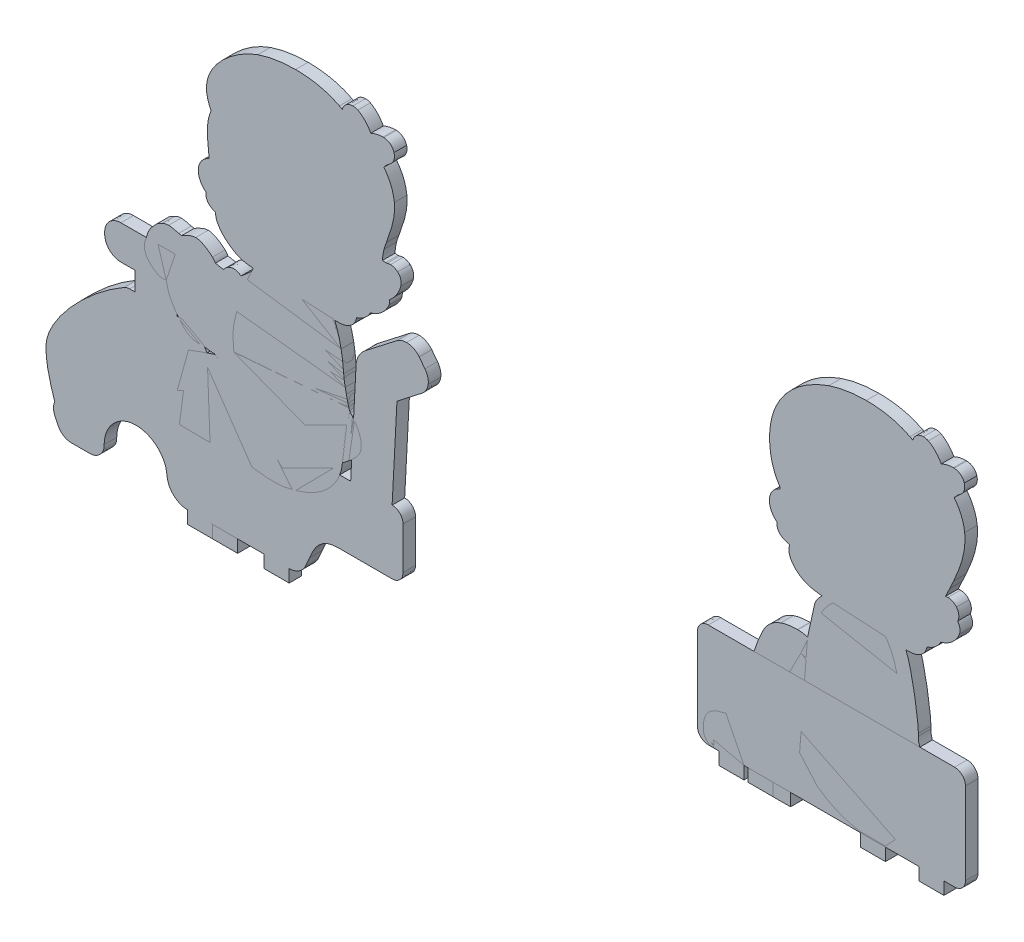
SolidWorks part; units mm, degrees
ref_plane "Front Plane" through (0, 0, 0) normal (0, 0, 1) x (1, 0, 0)
ref_plane "Top Plane" through (0, 0, 0) normal (0, 1, 0) x (1, 0, 0)
ref_plane "Right Plane" through (0, 0, 0) normal (1, 0, 0) x (0, 0, -1)
sketch "D-middle-laser" plane through (0, 0, 0) normal (0, 0, 1) x (1, 0, 0)
  line L0 (289.815, -387.2738) -> (287.7513, -387.2738)
  line L1 (289.9985, -383.7753) -> (289.815, -387.2738)
  line L2 (303.4169, -362.6517) -> (302.3566, -361.2835)
  line L3 (298.2586, -360.7635) -> (292.4293, -365.2856)
  line L4 (290.8054, -368.394) -> (290.3486, -377.102)
  line L5 (288.2912, -329.0773) -> (287.7488, -328.7908)
  line L6 (263.5287, -380.0569) -> (262.5101, -378.5259)
  line L7 (259.6897, -377.0034) -> (258.0098, -377.0034)
  line L8 (258.0098, -377.0034) -> (258.0098, -373.5654)
  line L9 (258.0098, -373.5654) -> (260.3237, -373.5654)
  line L10 (263.2848, -370.6043) -> (263.2848, -370.2876)
  line L11 (260.3237, -367.3265) -> (247.7387, -367.3265)
  line L12 (244.7776, -370.2876) -> (244.7776, -370.6043)
  line L13 (247.7387, -373.5654) -> (250.3211, -373.5654)
  line L14 (250.3211, -373.5654) -> (250.3211, -377.0034)
  line L15 (250.3211, -377.0034) -> (249.3468, -377.0034)
  line L16 (235.6813, -404.0488) -> (236.2843, -405.2726)
  line L17 (238.6679, -406.7577) -> (242.0233, -406.7577)
  line L18 (260.043, -406.7577) -> (278.5385, -406.7577)
  line L19 (287.9321, -398.9652) -> (297.408, -398.9652)
  line L20 (299.404, -396.9619) -> (299.404, -389.2771)
  line L21 (297.408, -387.2738) -> (297.4036, -387.2738)
  line L22 (297.4036, -387.2738) -> (298.292, -370.3419)
  line L23 (298.292, -370.3419) -> (302.8973, -366.7692)
  spline S0 degree 3 poles (287.7513, -387.2738) (288.0017, -386.4926) (288.1406, -385.7436) (288.2176, -385.16) knots 1 1 1 1 2 2 2 2
  spline S1 degree 3 poles (288.2176, -385.16) (288.7789, -384.7782) (289.4211, -384.2968) (289.9985, -383.7753) knots 2 2 2 2 3 3 3 3
  spline S2 degree 3 poles (302.3566, -361.2835) (301.7987, -360.5635) (300.9568, -360.1505) (300.0471, -360.1505) knots 1 1 1 1 2 2 2 2
  spline S3 degree 3 poles (300.0471, -360.1505) (299.4033, -360.1505) (298.7682, -360.3682) (298.2586, -360.7635) knots 2 2 2 2 3 3 3 3
  spline S4 degree 3 poles (292.4293, -365.2856) (291.4615, -366.0364) (290.8697, -367.1693) (290.8054, -368.394) knots 4 4 4 4 5 5 5 5
  spline S5 degree 3 poles (290.3486, -377.102) (290.1562, -376.851) (289.9602, -376.6271) (289.772, -376.4388) knots 6 6 6 6 7 7 7 7
  spline S6 degree 3 poles (289.772, -376.4388) (289.4986, -376.1311) (289.212, -374.765) (289.0223, -373.861) knots 7 7 7 7 8 8 8 8
  spline S7 degree 3 poles (289.0223, -373.861) (288.9555, -373.5426) (288.8874, -373.2183) (288.8144, -372.8929) knots 8 8 8 8 9 9 9 9
  spline S8 degree 3 poles (288.8144, -372.8929) (288.642, -372.1245) (288.5985, -371.5998) (288.5381, -370.8736) knots 9 9 9 9 10 10 10 10
  spline S9 degree 3 poles (288.5381, -370.8736) (288.4675, -370.023) (288.3796, -368.9644) (288.0679, -367.1711) knots 10 10 10 10 11 11 11 11
  spline S10 degree 3 poles (288.0679, -367.1711) (287.8122, -365.7003) (287.3659, -364.3238) (286.8927, -363.1609) knots 11 11 11 11 12 12 12 12
  spline S11 degree 3 poles (286.8927, -363.1609) (287.0416, -363.1791) (287.1753, -363.1899) (287.2919, -363.1959) knots 12 12 12 12 13 13 13 13
  spline S12 degree 3 poles (287.2919, -363.1959) (287.3941, -363.2011) (287.4917, -363.2036) (287.585, -363.2036) knots 13 13 13 13 14 14 14 14
  spline S13 degree 3 poles (287.585, -363.2036) (289.9033, -363.2036) (290.7438, -361.7222) (290.875, -360.8469) knots 14 14 14 14 15 15 15 15
  spline S14 degree 3 poles (290.875, -360.8469) (290.8775, -360.8303) (290.8799, -360.8136) (290.882, -360.797) knots 15 15 15 15 16 16 16 16
  spline S15 degree 3 poles (290.882, -360.797) (292.0577, -360.4417) (292.8744, -359.6931) (293.2711, -359.0262) knots 16 16 16 16 17 17 17 17
  spline S16 degree 3 poles (293.2711, -359.0262) (293.318, -358.9474) (293.3591, -358.8661) (293.3943, -358.783) knots 17 17 17 17 18 18 18 18
  spline S17 degree 3 poles (293.3943, -358.783) (293.4528, -358.7667) (293.511, -358.7498) (293.569, -358.7323) knots 18 18 18 18 19 19 19 19
  spline S18 degree 3 poles (293.569, -358.7323) (296.0101, -357.9939) (296.7701, -356.0179) (296.8488, -355.795) knots 19 19 19 19 20 20 20 20
  spline S19 degree 3 poles (296.8488, -355.795) (296.9513, -355.5043) (296.9891, -355.1985) (296.9622, -354.9012) knots 20 20 20 20 21 21 21 21
  spline S20 degree 3 poles (296.9622, -354.9012) (298.1734, -353.9098) (298.7918, -352.6042) (298.9896, -351.7798) knots 21 21 21 21 22 22 22 22
  spline S21 degree 3 poles (298.9896, -351.7798) (299.1632, -351.0562) (298.9762, -350.2768) (298.4188, -349.786) knots 22 22 22 22 23 23 23 23
  spline S22 degree 3 poles (298.4188, -349.786) (298.0425, -349.4547) (297.588, -349.2746) (297.1195, -349.2746) knots 23 23 23 23 24 24 24 24
  spline S23 degree 3 poles (297.1195, -349.2746) (296.9025, -349.2746) (296.6826, -349.3132) (296.466, -349.3933) knots 24 24 24 24 25 25 25 25
  spline S24 degree 3 poles (296.466, -349.3933) (296.4227, -349.402) (296.3247, -349.4182) (296.1972, -349.4182) knots 25 25 25 25 26 26 26 26
  spline S25 degree 3 poles (296.1972, -349.4182) (296.0085, -349.4182) (295.8332, -349.3836) (295.6743, -349.3152) knots 26 26 26 26 27 27 27 27
  spline S26 degree 3 poles (295.6743, -349.3152) (295.623, -349.011) (295.7022, -348.3839) (295.9104, -347.4465) knots 27 27 27 27 28 28 28 28
  spline S27 degree 3 poles (295.9104, -347.4465) (295.9612, -347.2177) (296.1733, -346.6388) (296.3604, -346.1281) knots 28 28 28 28 29 29 29 29
  spline S28 degree 3 poles (296.3604, -346.1281) (297.0823, -344.158) (298.0708, -341.4599) (297.813, -339.0739) knots 29 29 29 29 30 30 30 30
  spline S29 degree 3 poles (297.813, -339.0739) (297.5826, -336.9415) (296.623, -335.3648) (295.8968, -334.4484) knots 30 30 30 30 31 31 31 31
  spline S30 degree 3 poles (295.8968, -334.4484) (296.1152, -334.128) (296.5186, -333.703) (296.9482, -333.4073) knots 31 31 31 31 32 32 32 32
  spline S31 degree 3 poles (296.9482, -333.4073) (297.6676, -332.9237) (297.99, -332.0327) (297.7527, -331.1969) knots 32 32 32 32 33 33 33 33
  spline S32 degree 3 poles (297.7527, -331.1969) (297.5154, -330.3611) (296.7639, -329.7771) (295.8986, -329.7467) knots 33 33 33 33 34 34 34 34
  spline S33 degree 3 poles (295.8986, -329.7467) (295.8411, -329.7447) (295.7838, -329.7437) (295.7269, -329.7437) knots 34 34 34 34 35 35 35 35
  spline S34 degree 3 poles (295.7269, -329.7437) (294.895, -329.7437) (294.1468, -329.9513) (293.4967, -330.2559) knots 35 35 35 35 36 36 36 36
  spline S35 degree 3 poles (293.4967, -330.2559) (292.8111, -328.9444) (291.8316, -328.1275) (291.1317, -327.7714) knots 36 36 36 36 37 37 37 37
  spline S36 degree 3 poles (291.1317, -327.7714) (290.8428, -327.6244) (290.5346, -327.5546) (290.2308, -327.5546) knots 37 37 37 37 38 38 38 38
  spline S37 degree 3 poles (290.2308, -327.5546) (289.5218, -327.5546) (288.8367, -327.9348) (288.4757, -328.6015) knots 38 38 38 38 39 39 39 39
  spline S38 degree 3 poles (288.4757, -328.6015) (288.3925, -328.7551) (288.3313, -328.915) (288.2912, -329.0773) knots 39 39 39 39 40 40 40 40
  spline S39 degree 3 poles (287.7488, -328.7908) (285.0019, -327.3404) (281.8709, -327.0359) (279.7281, -327.0358) knots 41 41 41 41 42 42 42 42
  spline S40 degree 3 poles (279.7281, -327.0358) (277.2927, -327.0357) (274.84, -327.4258) (272.8218, -328.134) knots 43 43 43 43 44 44 44 44
  spline S41 degree 3 poles (272.8218, -328.134) (270.6039, -328.9125) (268.2296, -330.4012) (266.4707, -332.1165) knots 44 44 44 44 45 45 45 45
  spline S42 degree 3 poles (266.4707, -332.1165) (264.1293, -334.3998) (263.1008, -336.8128) (263.4964, -339.0948) knots 45 45 45 45 46 46 46 46
  spline S43 degree 3 poles (263.4964, -339.0948) (263.6216, -339.8165) (263.8793, -340.5475) (264.2658, -341.2784) knots 46 46 46 46 47 47 47 47
  spline S44 degree 3 poles (264.2658, -341.2784) (264.0578, -341.7935) (263.8519, -342.4295) (263.7162, -343.1598) knots 47 47 47 47 48 48 48 48
  spline S45 degree 3 poles (263.7162, -343.1598) (263.4474, -344.6049) (263.6585, -346.8017) (263.8775, -348.7474) knots 48 48 48 48 49 49 49 49
  spline S46 degree 3 poles (263.8775, -348.7474) (263.8922, -348.8774) (263.9054, -348.9946) (263.9165, -349.096) knots 49 49 49 49 50 50 50 50
  spline S47 degree 3 poles (263.9165, -349.096) (263.3073, -349.3249) (262.7746, -349.7324) (262.4163, -350.2673) knots 50 50 50 50 51 51 51 51
  spline S48 degree 3 poles (262.4163, -350.2673) (261.8528, -351.1083) (261.7663, -352.1733) (262.1788, -353.1892) knots 51 51 51 51 52 52 52 52
  spline S49 degree 3 poles (262.1788, -353.1892) (262.4294, -353.8064) (262.8184, -354.3024) (263.3046, -354.6489) knots 52 52 52 52 53 53 53 53
  spline S50 degree 3 poles (263.3046, -354.6489) (263.2765, -354.8621) (263.2826, -355.0805) (263.3246, -355.2958) knots 53 53 53 53 54 54 54 54
  spline S51 degree 3 poles (263.3246, -355.2958) (263.431, -355.841) (263.7581, -356.3174) (264.228, -356.6112) knots 54 54 54 54 55 55 55 55
  spline S52 degree 3 poles (264.228, -356.6112) (264.3474, -356.6859) (264.6348, -356.8483) (265.0896, -357.0027) knots 55 55 55 55 56 56 56 56
  spline S53 degree 3 poles (265.0896, -357.0027) (265.0759, -357.1621) (265.0811, -357.3246) (265.1067, -357.4867) knots 56 56 56 56 57 57 57 57
  spline S54 degree 3 poles (265.1067, -357.4867) (265.3252, -358.871) (266.6206, -360.3913) (268.5721, -361.5535) knots 57 57 57 57 58 58 58 58
  spline S55 degree 3 poles (268.5721, -361.5535) (269.4092, -362.052) (270.5449, -362.3431) (271.9558, -362.4217) knots 58 58 58 58 59 59 59 59
  spline S56 degree 3 poles (271.9558, -362.4217) (270.3159, -365.6075) (268.7289, -370.9204) (268.3691, -373.4038) knots 59 59 59 59 60 60 60 60
  spline S57 degree 3 poles (268.3691, -373.4038) (268.1946, -374.6086) (268.289, -375.6163) (268.3648, -376.4259) knots 60 60 60 60 61 61 61 61
  spline S58 degree 3 poles (268.3648, -376.4259) (268.4004, -376.8065) (268.4485, -377.3203) (268.4109, -377.507) knots 61 61 61 61 62 62 62 62
  spline S59 degree 3 poles (268.4109, -377.507) (268.41, -377.5078) (268.409, -377.5087) (268.408, -377.5096) knots 62 62 62 62 63 63 63 63
  spline S60 degree 3 poles (268.408, -377.5096) (267.8011, -378.0511) (267.3856, -378.557) (267.1083, -379.019) knots 63 63 63 63 64 64 64 64
  spline S61 degree 3 poles (267.1083, -379.019) (265.5866, -379.3829) (264.3897, -379.7552) (263.5287, -380.0569) knots 64 64 64 64 65 65 65 65
  spline S62 degree 3 poles (262.5101, -378.5259) (261.8831, -377.5723) (260.8296, -377.0034) (259.6897, -377.0034) knots 66 66 66 66 67 67 67 67
  spline S63 degree 3 poles (260.3237, -373.5654) (261.9565, -373.5654) (263.2848, -372.2371) (263.2848, -370.6043) knots 70 70 70 70 71 71 71 71
  spline S64 degree 3 poles (263.2848, -370.2876) (263.2848, -368.6548) (261.9565, -367.3265) (260.3237, -367.3265) knots 72 72 72 72 73 73 73 73
  spline S65 degree 3 poles (247.7387, -367.3265) (246.106, -367.3265) (244.7776, -368.6548) (244.7776, -370.2876) knots 74 74 74 74 75 75 75 75
  spline S66 degree 3 poles (244.7776, -370.6043) (244.7776, -372.2371) (246.106, -373.5654) (247.7387, -373.5654) knots 76 76 76 76 77 77 77 77
  spline S67 degree 3 poles (249.3468, -377.0034) (248.9989, -377.0034) (248.6571, -377.0946) (248.3552, -377.2681) knots 80 80 80 80 81 81 81 81
  spline S68 degree 3 poles (248.3552, -377.2681) (241.2374, -381.3575) (234.5679, -388.7784) (234.0825, -393.1489) knots 81 81 81 81 82 82 82 82
  spline S69 degree 3 poles (234.0825, -393.1489) (233.7752, -395.9162) (234.9563, -399.8057) (235.6424, -401.7681) knots 82 82 82 82 83 83 83 83
  spline S70 degree 3 poles (235.6424, -401.7681) (235.3137, -402.4919) (235.3233, -403.322) (235.6813, -404.0488) knots 83 83 83 83 84 84 84 84
  spline S71 degree 3 poles (236.2843, -405.2726) (236.7357, -406.1886) (237.649, -406.7577) (238.6679, -406.7577) knots 85 85 85 85 86 86 86 86
  spline S72 degree 3 poles (242.0233, -406.7577) (242.8394, -406.7577) (243.5707, -406.3871) (244.0588, -405.8049) knots 87 87 87 87 88 88 88 88
  spline S73 degree 3 poles (244.0588, -405.8049) (244.4475, -405.3411) (244.6819, -404.8566) (244.6819, -404.0353) knots 88 88 88 88 89 89 89 89
  spline S74 degree 3 poles (244.6819, -404.0353) (244.721, -400.7145) (247.3433, -398.042) (250.4935, -398.042) knots 89 89 89 89 90 90 90 90
  spline S75 degree 3 poles (250.4935, -398.042) (252.901, -398.0452) (255.0156, -399.5006) (255.888, -401.7055) knots 90 90 90 90 91 91 91 91
  spline S76 degree 2 poles (255.888, -401.7055) (256.0263, -402.0573) (256.1904, -403.1652) knots 91 91 91 92 92 92
  spline S77 degree 3 poles (256.1904, -403.1652) (256.3332, -405.1702) (258.0066, -406.7577) (260.043, -406.7577) knots 92 92 92 92 93 93 93 93
  spline S78 degree 3 poles (278.5385, -406.7577) (279.7927, -406.7577) (280.9282, -406.0673) (281.502, -404.956) knots 94 94 94 94 95 95 95 95
  spline S79 degree 3 poles (281.502, -404.956) (281.7807, -404.4162) (282.0468, -403.8175) (282.2929, -403.1765) knots 95 95 95 95 96 96 96 96
  spline S80 degree 3 poles (282.2929, -403.1765) (283.76, -399.2895) (285.883, -398.9652) (287.9321, -398.9652) knots 96 96 96 96 97 97 97 97
  spline S81 degree 3 poles (297.408, -398.9652) (298.5103, -398.9652) (299.404, -398.0683) (299.404, -396.9619) knots 98 98 98 98 99 99 99 99
  spline S82 degree 3 poles (299.404, -389.2771) (299.404, -388.1707) (298.5103, -387.2738) (297.408, -387.2738) knots 100 100 100 100 101 101 101 101
  spline S83 degree 3 poles (302.8973, -366.7692) (303.5161, -366.2892) (303.9108, -365.5963) (304.0089, -364.8181) knots 104 104 104 104 105 105 105 105
  spline S84 degree 3 poles (304.0089, -364.8181) (304.107, -364.0402) (303.8967, -363.2708) (303.4169, -362.6517) knots 105 105 105 105 106 106 106 106
sketch "D-side-laser" plane through (0, 0, 0) normal (0, 0, 1) x (1, 0, 0)
  line L0 (258.8724, -363.7956) -> (258.3404, -363.713)
  line L1 (264.3225, -399.9794) -> (264.8876, -400.5621)
  line L2 (264.4342, -406.7579) -> (269.1376, -406.7578)
  line L3 (271.7782, -397.5499) -> (271.1682, -396.181)
  spline S0 degree 3 poles (282.6058, -359.1139) (282.1072, -359.1139) (281.6629, -359.1439) (280.9028, -359.3758) knots 0 0 0 0 1 1 1 1
  spline S1 degree 3 poles (280.9028, -359.3758) (271.5883, -360.7479) (274.754, -360.7348) (269.7234, -364.7792) knots 1 1 1 1 2 2 2 2
  spline S2 degree 3 poles (269.7234, -364.7792) (268.7295, -363.9377) (267.4104, -364.1744) (266.5573, -365.3236) knots 2 2 2 2 3 3 3 3
  spline S3 degree 3 poles (266.5573, -365.3236) (266.0018, -365.2869) (266.2521, -365.3272) (265.0515, -365.0781) knots 3 3 3 3 4 4 4 4
  spline S4 degree 3 poles (265.0515, -365.0781) (264.9233, -364.8265) (264.7473, -364.596) (264.5263, -364.3987) knots 4 4 4 4 5 5 5 5
  spline S5 degree 3 poles (264.5263, -364.3987) (264.1269, -364.0354) (262.689, -362.8164) (261.4362, -362.8161) knots 5 5 5 5 6 6 6 6
  spline S6 degree 3 poles (261.4362, -362.8161) (260.6627, -362.8317) (259.8359, -363.2708) (258.8724, -363.7956) knots 6 6 6 6 7 7 7 7
  spline S7 degree 3 poles (258.3404, -363.713) (257.1022, -363.3562) (256.6327, -363.3562) (256.4755, -363.3562) knots 8 8 8 8 9 9 9 9
  spline S8 degree 3 poles (256.4755, -363.3562) (256.009, -363.3545) (255.5534, -363.5026) (255.182, -363.7631) knots 9 9 9 9 10 10 10 10
  spline S9 degree 3 poles (255.182, -363.7631) (254.6194, -363.9475) (254.1374, -364.3086) (253.7967, -364.789) knots 10 10 10 10 11 11 11 11
  spline S10 degree 3 poles (253.7967, -364.789) (253.1126, -365.3355) (252.562, -366.51) (252.3633, -367.5542) knots 11 11 11 11 12 12 12 12
  spline S11 degree 3 poles (252.3633, -367.5542) (251.2923, -369.6011) (253.0842, -371.3132) (254.1131, -371.9161) knots 12 12 12 12 13 13 13 13
  spline S12 degree 3 poles (254.1131, -371.9161) (254.7944, -372.324) (255.3616, -372.4721) (256.0436, -372.2943) knots 13 13 13 13 14 14 14 14
  spline S13 degree 3 poles (256.0436, -372.2943) (256.3107, -373.71) (256.813, -375.173) (257.7301, -376.2928) knots 14 14 14 14 15 15 15 15
  spline S14 degree 3 poles (257.7301, -376.2928) (258.498, -377.1927) (259.0812, -378.1969) (259.9425, -378.7705) knots 15 15 15 15 16 16 16 16
  spline S15 degree 3 poles (259.9425, -378.7705) (260.7019, -379.2722) (261.5154, -379.3398) (262.211, -379.3398) knots 16 16 16 16 17 17 17 17
  spline S16 degree 3 poles (262.211, -379.3398) (262.818, -379.3398) (263.929, -379.4359) (265.0418, -379.5681) knots 17 17 17 17 18 18 18 18
  spline S17 degree 3 poles (265.0418, -379.5681) (263.4796, -380.0296) (262.8507, -380.307) (262.3605, -380.4828) knots 18 18 18 18 19 19 19 19
  spline S18 degree 3 poles (262.3605, -380.4828) (260.2826, -381.1932) (259.1333, -381.6529) (258.7225, -382.1908) knots 19 19 19 19 20 20 20 20
  spline S19 degree 3 poles (258.7225, -382.1908) (257.2004, -383.7907) (255.6448, -385.6617) (255.7607, -387.6755) knots 20 20 20 20 21 21 21 21
  spline S20 degree 3 poles (255.7607, -387.6755) (255.8678, -389.6128) (256.1339, -391.1358) (257.0844, -392.2716) knots 21 21 21 21 22 22 22 22
  spline S21 degree 3 poles (257.0844, -392.2716) (257.2857, -392.512) (257.7556, -393.0903) (258.4579, -393.962) knots 22 22 22 22 23 23 23 23
  spline S22 degree 3 poles (258.4579, -393.962) (257.9307, -396.0861) (258.8359, -397.102) (260.2656, -397.9986) knots 23 23 23 23 24 24 24 24
  spline S23 degree 3 poles (260.2656, -397.9986) (260.3694, -398.1372) (260.5502, -398.4904) (260.6429, -398.7403) knots 24 24 24 24 25 25 25 25
  spline S24 degree 3 poles (260.6429, -398.7403) (261.2099, -400.2596) (262.8754, -400.1649) (264.3225, -399.9794) knots 25 25 25 25 26 26 26 26
  spline S25 degree 3 poles (264.8876, -400.5621) (264.8761, -400.8642) (264.861, -401.1338) (264.8452, -401.3516) knots 27 27 27 27 28 28 28 28
  spline S26 degree 3 poles (264.8452, -401.3516) (263.4303, -401.9602) (263.1095, -403.2632) (263.0497, -404.357) knots 28 28 28 28 29 29 29 29
  spline S27 degree 3 poles (263.0497, -404.357) (263.0013, -405.2419) (263.2871, -406.1472) (264.1169, -406.6049) knots 29 29 29 29 30 30 30 30
  spline S28 degree 3 poles (264.1169, -406.6049) (264.2035, -406.6617) (264.3105, -406.7126) (264.4342, -406.7579) knots 30 30 30 30 31 31 31 31
  spline S29 degree 3 poles (269.1376, -406.7578) (269.5569, -406.6434) (269.7855, -406.5047) (270.0112, -406.3185) knots 32 32 32 32 33 33 33 33
  spline S30 degree 3 poles (270.0112, -406.3185) (270.6944, -405.7549) (271.0964, -404.6437) (271.6198, -403.843) knots 33 33 33 33 34 34 34 34
  spline S31 degree 3 poles (271.6198, -403.843) (274.3801, -402.3954) (273.859, -399.253) (271.7782, -397.5499) knots 34 34 34 34 35 35 35 35
  spline S32 degree 3 poles (271.1682, -396.181) (271.5506, -395.4655) (271.7903, -394.8059) (271.7325, -394.0699) knots 36 36 36 36 37 37 37 37
  spline S33 degree 3 poles (271.7325, -394.0699) (273.8858, -394.3648) (275.621, -394.521) (277.5174, -394.2955) knots 37 37 37 37 38 38 38 38
  spline S34 degree 3 poles (277.5174, -394.2955) (284.5141, -393.074) (287.9402, -389.2172) (288.3042, -385.1014) knots 38 38 38 38 39 39 39 39
  spline S35 degree 3 poles (288.3042, -385.1014) (289.413, -384.337) (290.8287, -383.1821) (291.4061, -382.1228) knots 39 39 39 39 40 40 40 40
  spline S36 degree 3 poles (291.4061, -382.1228) (292.4462, -380.2141) (290.9558, -377.6235) (289.7721, -376.4389) knots 40 40 40 40 41 41 41 41
  spline S37 degree 3 poles (289.7721, -376.4389) (289.361, -375.8714) (289.0546, -373.8832) (288.8143, -372.8924) knots 41 41 41 41 42 42 42 42
  spline S38 degree 3 poles (288.8143, -372.8924) (288.3854, -370.6784) (288.5882, -369.9812) (288.0677, -367.1711) knots 42 42 42 42 43 43 43 43
  spline S39 degree 3 poles (288.0677, -367.1711) (287.4299, -363.5002) (285.4132, -361.626) (284.9419, -360.9759) knots 43 43 43 43 44 44 44 44
  spline S40 degree 3 poles (284.9419, -360.9759) (284.8193, -360.6285) (284.2769, -359.9129) (283.7319, -359.4421) knots 44 44 44 44 45 45 45 45
  spline S41 degree 2 poles (283.7319, -359.4421) (283.311, -359.0814) (282.6058, -359.1139) knots 45 45 45 46 46 46
sketch "M-arm-laser" plane through (0, 0, 0) normal (0, 0, 1) x (1, 0, 0)
  line L0 (364.0273, -389.7021) -> (364.0193, -389.7589)
  line L1 (364.0193, -389.7589) -> (364.0308, -389.9127)
  line L2 (366.6578, -396.3371) -> (370.5698, -396.3371)
  spline S0 degree 3 poles (390.0078, -368.8827) (389.9756, -368.376) (388.9967, -361.5649) (384.207, -360.674) knots 0 0 0 0 1 1 1 1
  spline S1 degree 3 poles (384.207, -360.674) (383.7435, -360.5878) (378.9808, -359.8258) (375.9436, -365.1067) knots 1 1 1 1 2 2 2 2
  spline S2 degree 3 poles (375.9436, -365.1067) (375.5017, -365.875) (372.7612, -372.433) (372.3066, -373.2283) knots 2 2 2 2 3 3 3 3
  spline S3 degree 3 poles (372.3066, -373.2283) (371.926, -373.8946) (371.5017, -374.7354) (371.0913, -375.5485) knots 3 3 3 3 4 4 4 4
  spline S4 degree 3 poles (371.0913, -375.5485) (370.868, -375.9912) (370.5042, -376.7124) (370.2692, -377.1445) knots 4 4 4 4 5 5 5 5
  spline S5 degree 3 poles (370.2692, -377.1445) (370.2019, -377.2683) (370.114, -377.3758) (370.0062, -377.4666) knots 5 5 5 5 6 6 6 6
  spline S6 degree 3 poles (370.0062, -377.4666) (369.515, -377.8805) (368.7547, -378.5709) (368.0371, -379.3182) knots 6 6 6 6 7 7 7 7
  spline S7 degree 3 poles (368.0371, -379.3182) (365.9088, -381.5347) (365.563, -382.7539) (365.488, -383.4783) knots 7 7 7 7 8 8 8 8
  spline S8 degree 3 poles (365.488, -383.4783) (365.4643, -383.7088) (365.4275, -383.9492) (365.3886, -384.2036) knots 8 8 8 8 9 9 9 9
  spline S9 degree 3 poles (365.3886, -384.2036) (365.2827, -384.8957) (365.1611, -385.6904) (365.2595, -386.5255) knots 9 9 9 9 10 10 10 10
  spline S10 degree 3 poles (365.2595, -386.5255) (365.2919, -386.8) (365.221, -387.0788) (365.0645, -387.3068) knots 10 10 10 10 11 11 11 11
  spline S11 degree 3 poles (365.0645, -387.3068) (364.1713, -388.6083) (364.0664, -389.0249) (364.0356, -389.4264) knots 11 11 11 11 12 12 12 12
  spline S12 degree 3 poles (364.0356, -389.4264) (364.0316, -389.4786) (364.0269, -389.56) (364.0273, -389.7021) knots 12 12 12 12 13 13 13 13
  spline S13 degree 3 poles (364.0308, -389.9127) (364.0529, -390.7024) (364.4878, -392.9862) (365.0612, -394.1583) knots 15 15 15 15 16 16 16 16
  spline S14 degree 3 poles (365.0612, -394.1583) (365.2529, -394.5502) (366.2215, -396.3371) (366.6578, -396.3371) knots 16 16 16 16 17 17 17 17
  spline S15 degree 3 poles (370.5698, -396.3371) (370.9408, -396.3371) (372.1858, -394.7129) (372.48, -392.4929) knots 18 18 18 18 19 19 19 19
  spline S16 degree 3 poles (372.48, -392.4929) (372.5415, -392.5076) (372.6526, -392.5375) (372.7238, -392.5566) knots 19 19 19 19 20 20 20 20
  spline S17 degree 3 poles (372.7238, -392.5566) (373.2659, -392.7024) (374.1727, -392.9462) (375.2608, -392.9462) knots 20 20 20 20 21 21 21 21
  spline S18 degree 3 poles (375.2608, -392.9462) (376.6927, -392.9462) (377.9986, -392.5259) (379.1423, -391.6968) knots 21 21 21 21 22 22 22 22
  spline S19 degree 3 poles (379.1423, -391.6968) (381.1661, -390.2294) (381.6345, -389.2488) (382.0015, -388.2084) knots 22 22 22 22 23 23 23 23
  spline S20 degree 3 poles (382.0015, -388.2084) (382.0612, -388.0391) (382.1043, -387.9168) (382.162, -387.8015) knots 23 23 23 23 24 24 24 24
  spline S21 degree 3 poles (382.162, -387.8015) (382.5504, -387.0249) (385.0879, -383.1352) (386.2978, -381.6625) knots 24 24 24 24 25 25 25 25
  spline S22 degree 3 poles (386.2978, -381.6625) (387.6594, -380.0052) (390.4456, -373.507) (390.0078, -368.8827) knots 25 25 25 25 26 26 26 26
sketch "M-middle-laser" plane through (0, 0, 0) normal (0, 0, 1) x (1, 0, 0)
  line L0 (371.6951, -369.8906) -> (371.6119, -369.8911)
  line L1 (356.4013, -396.3342) -> (367.3662, -396.3371)
  line L2 (370.1145, -391.8785) -> (369.9936, -391.2546)
  line L3 (392.7498, -329.2933) -> (392.2096, -329.0091)
  spline S0 degree 3 poles (384.2217, -327.2663) (381.7955, -327.2663) (379.3515, -327.6537) (377.3398, -328.3572) knots 1 1 1 1 2 2 2 2
  spline S1 degree 3 poles (377.3398, -328.3572) (375.472, -329.0104) (372.7696, -330.2539) (370.5029, -332.4686) knots 2 2 2 2 3 3 3 3
  spline S2 degree 3 poles (370.5029, -332.4686) (367.6335, -335.2722) (366.268, -338.9309) (366.5539, -343.0493) knots 3 3 3 3 4 4 4 4
  spline S3 degree 3 poles (366.5539, -343.0493) (366.6222, -344.0294) (366.7977, -346.5467) (368.4399, -348.9053) knots 4 4 4 4 5 5 5 5
  spline S4 degree 3 poles (368.4399, -348.9053) (368.4506, -349.0003) (368.4603, -349.0864) (368.4687, -349.1629) knots 5 5 5 5 6 6 6 6
  spline S5 degree 3 poles (368.4687, -349.1629) (367.9888, -349.3427) (367.554, -349.6331) (367.2182, -350.0104) knots 6 6 6 6 7 7 7 7
  spline S6 degree 3 poles (367.2182, -350.0104) (366.4491, -350.8755) (366.2696, -352.0769) (366.7375, -353.2251) knots 7 7 7 7 8 8 8 8
  spline S7 degree 3 poles (366.7375, -353.2251) (366.9875, -353.8387) (367.3751, -354.3319) (367.8593, -354.6765) knots 8 8 8 8 9 9 9 9
  spline S8 degree 3 poles (367.8593, -354.6765) (367.8316, -354.8876) (367.8375, -355.1035) (367.8789, -355.3156) knots 9 9 9 9 10 10 10 10
  spline S9 degree 3 poles (367.8789, -355.3156) (367.9846, -355.8556) (368.3129, -356.3316) (368.7796, -356.6221) knots 10 10 10 10 11 11 11 11
  spline S10 degree 3 poles (368.7796, -356.6221) (368.9425, -356.7237) (369.4238, -356.9912) (370.2222, -357.1753) knots 11 11 11 11 12 12 12 12
  spline S11 degree 3 poles (370.2222, -357.1753) (370.0574, -357.5273) (369.9931, -357.9289) (370.0565, -358.3301) knots 12 12 12 12 13 13 13 13
  spline S12 degree 3 poles (370.0565, -358.3301) (370.3279, -360.0446) (372.1776, -361.457) (373.7802, -361.9157) knots 13 13 13 13 14 14 14 14
  spline S13 degree 3 poles (373.7802, -361.9157) (374.5048, -362.1226) (375.3399, -362.2369) (376.1346, -362.2972) knots 14 14 14 14 15 15 15 15
  spline S14 degree 3 poles (376.1346, -362.2972) (375.488, -362.8725) (374.932, -363.5735) (374.7399, -364.3739) knots 15 15 15 15 16 16 16 16
  spline S15 degree 3 poles (374.7399, -364.3739) (374.3171, -366.1349) (373.8433, -368.3076) (373.4728, -370.1577) knots 16 16 16 16 17 17 17 17
  spline S16 degree 3 poles (373.4728, -370.1577) (372.9088, -369.9818) (372.311, -369.8906) (371.6951, -369.8906) knots 17 17 17 17 18 18 18 18
  spline S17 degree 3 poles (371.6119, -369.8911) (370.1433, -369.915) (369.4071, -370.0769) (368.5604, -370.3674) knots 19 19 19 19 20 20 20 20
  spline S18 degree 3 poles (368.5604, -370.3674) (367.0946, -370.8712) (366.0171, -371.8232) (365.2653, -373.2779) knots 20 20 20 20 21 21 21 21
  spline S19 degree 3 poles (365.2653, -373.2779) (364.479, -374.799) (363.5793, -377.3167) (362.8588, -380.0126) knots 21 21 21 21 22 22 22 22
  spline S20 degree 3 poles (362.8588, -380.0126) (361.951, -383.4077) (361.4587, -386.245) (361.3689, -386.7845) knots 22 22 22 22 23 23 23 23
  spline S21 degree 3 poles (361.3689, -386.7845) (361.3088, -387.0825) (361.2325, -387.6097) (361.2823, -388.2025) knots 23 23 23 23 24 24 24 24
  spline S22 degree 3 poles (361.2823, -388.2025) (360.0815, -388.9858) (358.6825, -389.7356) (357.6352, -389.9558) knots 24 24 24 24 25 25 25 25
  spline S23 degree 3 poles (357.6352, -389.9558) (354.7372, -390.5645) (354.2701, -392.7387) (354.3886, -394.4555) knots 25 25 25 25 26 26 26 26
  spline S24 degree 3 poles (354.3886, -394.4555) (354.4617, -395.5092) (355.3458, -396.3342) (356.4013, -396.3342) knots 26 26 26 26 27 27 27 27
  spline S25 degree 3 poles (367.3662, -396.3371) (367.6818, -396.3371) (367.9969, -396.2619) (368.278, -396.1195) knots 28 28 28 28 29 29 29 29
  spline S26 degree 3 poles (368.278, -396.1195) (369.176, -395.6666) (370.5765, -394.262) (370.1145, -391.8785) knots 29 29 29 29 30 30 30 30
  spline S27 degree 3 poles (369.9936, -391.2546) (370.2478, -391.0022) (370.526, -390.708) (370.8469, -390.3611) knots 31 31 31 31 32 32 32 32
  spline S28 degree 3 poles (370.8469, -390.3611) (371.084, -390.1049) (371.3232, -389.8464) (371.4755, -389.7018) knots 32 32 32 32 33 33 33 33
  spline S29 degree 3 poles (371.4755, -389.7018) (371.6049, -389.5788) (371.7614, -389.4349) (371.9315, -389.2785) knots 33 33 33 33 34 34 34 34
  spline S30 degree 3 poles (371.9315, -389.2785) (371.9578, -389.2543) (371.9838, -389.2303) (372.0096, -389.2065) knots 34 34 34 34 35 35 35 35
  spline S31 degree 3 poles (372.0096, -389.2065) (372.5753, -390.2565) (373.1118, -391.0291) (373.613, -391.5138) knots 35 35 35 35 36 36 36 36
  spline S32 degree 3 poles (373.613, -391.5138) (376.8554, -394.6481) (380.9413, -396.3048) (385.4292, -396.3048) knots 36 36 36 36 37 37 37 37
  spline S33 degree 3 poles (385.4292, -396.3048) (390.986, -396.3048) (394.7078, -394.0763) (395.9091, -390.0298) knots 37 37 37 37 38 38 38 38
  spline S34 degree 3 poles (395.9091, -390.0298) (396.7336, -387.251) (397.2485, -384.5859) (395.1899, -380.0981) knots 38 38 38 38 39 39 39 39
  spline S35 degree 3 poles (395.1899, -380.0981) (393.7414, -376.9407) (393.7467, -376.6136) (393.7609, -375.7392) knots 39 39 39 39 40 40 40 40
  spline S36 degree 3 poles (393.7609, -375.7392) (393.7633, -375.5959) (393.7657, -375.4418) (393.7657, -375.2722) knots 40 40 40 40 41 41 41 41
  spline S37 degree 3 poles (393.7657, -375.2722) (393.7657, -373.5678) (392.7231, -366.1031) (391.4727, -363.1352) knots 41 41 41 41 42 42 42 42
  spline S38 degree 3 poles (391.4727, -363.1352) (391.576, -363.1459) (391.6703, -363.1528) (391.7544, -363.1571) knots 42 42 42 42 43 43 43 43
  spline S39 degree 3 poles (391.7544, -363.1571) (391.8557, -363.1622) (391.9521, -363.1645) (392.0443, -363.1645) knots 43 43 43 43 44 44 44 44
  spline S40 degree 3 poles (392.0443, -363.1645) (394.3453, -363.1645) (395.1876, -361.6998) (395.3226, -360.8344) knots 44 44 44 44 45 45 45 45
  spline S41 degree 3 poles (395.3226, -360.8344) (395.3253, -360.8164) (395.3277, -360.7984) (395.3299, -360.7804) knots 45 45 45 45 46 46 46 46
  spline S42 degree 3 poles (395.3299, -360.7804) (396.5036, -360.4277) (397.3181, -359.6801) (397.713, -359.0144) knots 46 46 46 46 47 47 47 47
  spline S43 degree 3 poles (397.713, -359.0144) (397.7589, -358.9376) (397.7991, -358.8583) (397.8336, -358.777) knots 47 47 47 47 48 48 48 48
  spline S44 degree 3 poles (397.8336, -358.777) (397.8923, -358.7608) (397.9505, -358.744) (398.0083, -358.7266) knots 48 48 48 48 49 49 49 49
  spline S45 degree 3 poles (398.0083, -358.7266) (400.4424, -357.993) (401.1972, -356.0307) (401.2752, -355.8094) knots 49 49 49 49 50 50 50 50
  spline S46 degree 3 poles (401.2752, -355.8094) (401.5056, -355.1608) (401.3797, -354.4348) (400.9468, -353.8986) knots 50 50 50 50 51 51 51 51
  spline S47 degree 3 poles (400.9468, -353.8986) (401.2904, -353.2217) (401.2156, -352.3871) (400.7435, -351.7788) knots 51 51 51 51 52 52 52 52
  spline S48 degree 3 poles (400.7435, -351.7788) (400.3702, -351.2977) (399.7826, -351.0104) (399.1718, -351.0103) knots 52 52 52 52 53 53 53 53
  spline S49 degree 3 poles (399.1718, -351.0103) (399.028, -351.0103) (398.885, -351.0257) (398.7451, -351.0564) knots 53 53 53 53 54 54 54 54
  spline S50 degree 3 poles (398.7451, -351.0564) (398.9474, -350.5507) (399.266, -349.8992) (399.4874, -349.4464) knots 54 54 54 54 55 55 55 55
  spline S51 degree 3 poles (399.4874, -349.4464) (399.7389, -348.932) (399.9915, -348.4151) (400.2216, -347.8879) knots 55 55 55 55 56 56 56 56
  spline S52 degree 3 poles (400.2216, -347.8879) (401.2202, -345.6009) (402.5881, -342.4681) (402.2353, -339.2152) knots 56 56 56 56 57 57 57 57
  spline S53 degree 3 poles (402.2353, -339.2152) (402.0061, -337.1026) (401.0428, -335.5308) (400.3259, -334.6262) knots 57 57 57 57 58 58 58 58
  spline S54 degree 3 poles (400.3259, -334.6262) (400.5429, -334.3079) (400.9453, -333.8868) (401.3763, -333.5893) knots 58 58 58 58 59 59 59 59
  spline S55 degree 3 poles (401.3763, -333.5893) (402.0907, -333.0979) (402.4058, -332.2225) (402.17, -331.3982) knots 60 60 60 60 61 61 61 61
  spline S56 degree 3 poles (402.17, -331.3982) (401.9325, -330.567) (401.1922, -329.9879) (400.328, -329.9577) knots 61 61 61 61 62 62 62 62
  spline S57 degree 3 poles (400.328, -329.9577) (400.2702, -329.9559) (400.218, -329.9551) (400.1663, -329.9551) knots 62 62 62 62 63 63 63 63
  spline S58 degree 3 poles (400.1663, -329.9551) (399.4199, -329.955) (398.6686, -330.1298) (397.9462, -330.4635) knots 63 63 63 63 64 64 64 64
  spline S59 degree 3 poles (397.9462, -330.4635) (397.0752, -328.8043) (395.7775, -328.0977) (395.5803, -327.9976) knots 64 64 64 64 65 65 65 65
  spline S60 degree 3 poles (395.5803, -327.9976) (395.3008, -327.8564) (394.9909, -327.7826) (394.6812, -327.7826) knots 65 65 65 65 66 66 66 66
  spline S61 degree 3 poles (394.6812, -327.7826) (393.9536, -327.7825) (393.2846, -328.1791) (392.9355, -328.8177) knots 66 66 66 66 67 67 67 67
  spline S62 degree 3 poles (392.9355, -328.8177) (392.8519, -328.9718) (392.7903, -329.1315) (392.7498, -329.2933) knots 67 67 67 67 68 68 68 68
  spline S63 degree 3 poles (392.2096, -329.0091) (389.4721, -327.5688) (386.3548, -327.2664) (384.2217, -327.2663) knots 69 69 69 69 70 70 70 70
base flange "d-torso" sketch "D-middle-laser" thickness 2.3 reverse thickness direction no parameters "D1"=0.7366
sketch "Sketch10" plane through (0, 0, 0) normal (0, 0, 1) x (1, 0, 0)
  line L0 (260.043, -406.7577) -> (278.5385, -406.7577) construction
  line L1 (259.9584, -406.7577) -> (264.5584, -406.7577)
  line L2 (259.9584, -406.7577) -> (259.9584, -409.0577)
  line L3 (259.9584, -409.0577) -> (264.5584, -409.0577)
  line L4 (264.5584, -406.7577) -> (264.5584, -409.0577)
  line L6 (278.5584, -406.7577) -> (273.9584, -406.7577)
  line L7 (278.5584, -406.7577) -> (278.5584, -409.0577)
  line L8 (278.5584, -409.0577) -> (273.9584, -409.0577)
  line L9 (273.9584, -406.7577) -> (273.9584, -409.0577)
  dimension "D1" = 4.6
  dimension "D2" = 2.3
  dimension "D3" = 9.4
base flange "Tab1" sketch "Sketch10" thickness 2.3 reverse thickness direction no parameters "D1"=0.7366
base flange "d-side" sketch "D-side-laser" thickness 2.3 reverse thickness direction no parameters "D1"=0.7366
sketch "Sketch15" plane through (0, 0, 0) normal (0, 0, 1) x (1, 0, 0)
  line L1 (264.5212, -406.7578) -> (269.1212, -406.7578)
  line L2 (264.5212, -406.7578) -> (264.5212, -409.0578)
  line L3 (264.5212, -409.0578) -> (269.1212, -409.0578)
  line L4 (269.1212, -406.7578) -> (269.1212, -409.0578)
  dimension "D1" = 2.3
  dimension "D2" = 4.6
base flange "Tab2" sketch "Sketch15" thickness 2.3 reverse thickness direction no parameters "D1"=0.7366
base flange "m-torso" sketch "M-middle-laser" thickness 2.3 reverse thickness direction no parameters "D1"=0.7366
sketch "Sketch20" plane through (0, 0, 0) normal (0, 0, 1) x (1, 0, 0)
  line L0 (385.4292, -396.3048) -> (385.4292, -391.2548) construction
  line L1 (383.1292, -398.6371) -> (387.7292, -398.6371)
  line L2 (387.7292, -398.6371) -> (387.7292, -395.0512)
  line L3 (387.7292, -395.0512) -> (383.1292, -395.0512)
  line L4 (383.1292, -398.6371) -> (383.1292, -395.0512)
  line L6 (367.1292, -395.9198) -> (362.5292, -395.9198)
  line L7 (367.1292, -395.9198) -> (367.1292, -398.6371)
  line L8 (367.1292, -398.6371) -> (362.5292, -398.6371)
  line L9 (362.5292, -395.9198) -> (362.5292, -398.6371)
  point P9 (385.4292, -395.0512)
  point P10 (385.4292, -398.6371)
  point P16 (0, 0)
  point P17 (0, 0)
  dimension "D1" = 16
  dimension "D2" = 2.3
  dimension "D4" = 4.6
base flange "Tab3" sketch "Sketch20" thickness 2.3 reverse thickness direction no parameters "D1"=0.7366
sketch "M-side-laser" plane through (0, 0, 0) normal (0, 0, 1) x (1, 0, 0)
  line L0 (400.3857, -377.3278) -> (355.2958, -377.3278)
  line L1 (353.306, -379.3175) -> (353.306, -394.3475)
  line L2 (355.2958, -396.3371) -> (400.3857, -396.3371)
  line L3 (402.3753, -394.3475) -> (402.3753, -379.3175)
  spline S0 degree 3 poles (355.2958, -377.3278) (354.1986, -377.3278) (353.306, -378.2204) (353.306, -379.3175) knots 1 1 1 1 2 2 2 2
  spline S1 degree 3 poles (353.306, -394.3475) (353.306, -395.4446) (354.1986, -396.3371) (355.2958, -396.3371) knots 3 3 3 3 4 4 4 4
  spline S2 degree 3 poles (400.3857, -396.3371) (401.4828, -396.3371) (402.3753, -395.4446) (402.3753, -394.3475) knots 5 5 5 5 6 6 6 6
  spline S3 degree 3 poles (402.3753, -379.3175) (402.3753, -378.2204) (401.4828, -377.3278) (400.3857, -377.3278) knots 7 7 7 7 8 8 8 8
base flange "box" sketch "M-side-laser" thickness 2.3 reverse thickness direction no parameters "D1"=0.7366
sketch "Sketch25" plane through (0, 0, 0) normal (0, 0, 1) x (1, 0, 0)
  line L0 (355.2958, -396.3371) -> (400.3857, -396.3371) construction
  line L1 (357.2408, -396.3371) -> (361.8408, -396.3371)
  line L2 (357.2408, -396.3371) -> (357.2408, -398.6371)
  line L3 (357.2408, -398.6371) -> (361.8408, -398.6371)
  line L4 (361.8408, -396.3371) -> (361.8408, -398.6371)
  line L5 (377.8408, -396.3371) -> (377.8408, -377.3278) construction
  line L7 (393.8408, -396.3371) -> (393.8408, -398.6371)
  line L8 (398.4408, -398.6371) -> (393.8408, -398.6371)
  line L9 (398.4408, -396.3371) -> (398.4408, -398.6371)
  line L10 (398.4408, -396.3371) -> (393.8408, -396.3371)
  point P6 (377.8408, -396.3371)
  dimension "D1" = 2.3
  dimension "D2" = 4.6
  dimension "D3" = 16
base flange "Tab4" sketch "Sketch25" thickness 2.3 reverse thickness direction no parameters "D1"=0.7366
base flange "m-arm" sketch "M-arm-laser" thickness 2.3 reverse thickness direction no parameters "D1"=0.7366
sketch "Sketch30" plane through (0, 0, 0) normal (0, 0, 1) x (1, 0, 0)
  line L0 (366.6578, -396.3371) -> (370.5698, -396.3371) construction
  line L1 (366.9002, -396.3371) -> (370.3502, -396.3371)
  line L2 (366.9002, -396.3371) -> (366.9002, -398.6371)
  line L3 (366.9002, -398.6371) -> (370.3502, -398.6371)
  line L4 (370.3502, -396.3371) -> (370.3502, -398.6371)
  dimension "D1" = 2.3
  dimension "D2" = 3.45
base flange "Tab5" sketch "Sketch30" thickness 2.3 reverse thickness direction no parameters "D1"=0.7366
sketch "Bend-Lines1" [suppressed] plane through (0, 0, 0) normal (0, 1, 0) x (1, 0, 0)
sketch "Bounding-Box1" [suppressed] plane through (0, 0, 0) normal (0, 1, 0) x (1, 0, 0)
sheet metal parameters "Sheet-Metal1" thickness 2.3 parameters "D1"=0.7366
flat pattern "Flat-Pattern1" [suppressed]
sketch "Bend-Lines2" plane through (0, 0, 0) normal (0, 1, 0) x (1, 0, 0)
sketch3d "Bounding-Box2" [suppressed]
  line L0 (2.6985, 33.4112, 0) -> (2.6985, -46.3107, 0) construction
  line L1 (-67.3012, 33.4112, 0) -> (-67.3012, -46.3107, 0) construction
  line L2 (2.6985, 33.4112, 0) -> (-67.3012, 33.4112, 0) construction
  line L3 (2.6985, -46.3107, 0) -> (-67.3012, -46.3107, 0) construction
sheet metal parameters "Sheet-Metal2" thickness 2.3 parameters "D1"=0.7366
flat pattern "Flat-Pattern2"
sketch "Bend-Lines3" plane through (0, 0, 0) normal (0, 1, 0) x (1, 0, 0)
sketch3d "Bounding-Box3" [suppressed]
  line L0 (-4.494, -54.6353, 0) -> (7.6126, 30.2426, 0) construction
  line L1 (-69.0684, -45.4247, 0) -> (-56.9618, 39.4532, 0) construction
  line L2 (-4.494, -54.6353, 0) -> (-69.0684, -45.4247, 0) construction
  line L3 (7.6126, 30.2426, 0) -> (-56.9618, 39.4532, 0) construction
sheet metal parameters "Sheet-Metal3" thickness 2.3 parameters "D1"=0.7366
flat pattern "Flat-Pattern3"
sketch "Bend-Lines4" plane through (0, 0, 0) normal (0, 1, 0) x (1, 0, 0)
sketch3d "Bounding-Box4" [suppressed]
  line L0 (-4.1366, 1.7753, 0) -> (-12.5994, -42.4709, 0) construction
  line L1 (32.1117, -5.1578, 0) -> (23.6489, -49.404, 0) construction
  line L2 (-4.1366, 1.7753, 0) -> (32.1117, -5.1578, 0) construction
  line L3 (-12.5994, -42.4709, 0) -> (23.6489, -49.404, 0) construction
sheet metal parameters "Sheet-Metal4" thickness 2.3 parameters "D1"=0.7366
flat pattern "Flat-Pattern4"
sketch "Bend-Lines5" plane through (0, 0, 0) normal (0, 1, 0) x (1, 0, 0)
sketch3d "Bounding-Box5" [suppressed]
  line L0 (4.1366, 1.7753, 0) -> (13.0232, -44.6868, 0) construction
  line L1 (-32.1117, -5.1578, 0) -> (-23.2251, -51.6198, 0) construction
  line L2 (4.1366, 1.7753, 0) -> (-32.1117, -5.1578, 0) construction
  line L3 (13.0232, -44.6868, 0) -> (-23.2251, -51.6198, 0) construction
sheet metal parameters "Sheet-Metal5" thickness 2.3 parameters "D1"=0.7366
flat pattern "Flat-Pattern5"
sketch "Bend-Lines6" plane through (0, 0, 0) normal (0, 1, 0) x (1, 0, 0)
sketch3d "Bounding-Box6" [suppressed]
  line L0 (-6.3053, -74.5035, 0) -> (-17.3295, -1.7752, 0) construction
  line L1 (33.9873, -68.3959, 0) -> (22.963, 4.3324, 0) construction
  line L2 (-6.3053, -74.5035, 0) -> (33.9873, -68.3959, 0) construction
  line L3 (-17.3295, -1.7752, 0) -> (22.963, 4.3324, 0) construction
sheet metal parameters "Sheet-Metal6" thickness 2.3 parameters "D1"=0.7366
flat pattern "Flat-Pattern6"
sketch "Bend-Lines7" plane through (0, 0, 0) normal (0, 1, 0) x (1, 0, 0)
sketch3d "Bounding-Box7" [suppressed]
  line L0 (4.4333, -77.893, 0) -> (21.4833, -3.5253, 0) construction
  line L1 (-34.3601, -68.9989, 0) -> (-17.3101, 5.3688, 0) construction
  line L2 (4.4333, -77.893, 0) -> (-34.3601, -68.9989, 0) construction
  line L3 (21.4833, -3.5253, 0) -> (-17.3101, 5.3688, 0) construction
sheet metal parameters "Sheet-Metal7" thickness 2.3 parameters "D1"=0.7366
flat pattern "Flat-Pattern7"
sketch "Bend-Lines8" plane through (0, 0, 0) normal (0, 1, 0) x (1, 0, 0)
sketch3d "Bounding-Box8" [suppressed]
  line L0 (0.5835, -18.4259, 0) -> (-48.4859, -18.4259, 0) construction
  line L1 (0.5835, 0.5834, 0) -> (-48.4859, 0.5834, 0) construction
  line L2 (0.5835, -18.4259, 0) -> (0.5835, 0.5834, 0) construction
  line L3 (-48.4859, -18.4259, 0) -> (-48.4859, 0.5834, 0) construction
sheet metal parameters "Sheet-Metal8" thickness 2.3 parameters "D1"=0.7366
flat pattern "Flat-Pattern8"
sketch "Bend-Lines9" plane through (0, 0, 0) normal (0, 1, 0) x (1, 0, 0)
sketch3d "Bounding-Box9" [suppressed]
  line L0 (-0.5835, -20.7259, 0) -> (48.4859, -20.7259, 0) construction
  line L1 (-0.5835, 0.5834, 0) -> (48.4859, 0.5834, 0) construction
  line L2 (-0.5835, -20.7259, 0) -> (-0.5835, 0.5834, 0) construction
  line L3 (48.4859, -20.7259, 0) -> (48.4859, 0.5834, 0) construction
sheet metal parameters "Sheet-Metal9" thickness 2.3 parameters "D1"=0.7366
flat pattern "Flat-Pattern9"
sketch "Bend-Lines10" plane through (0, 0, 0) normal (0, 1, 0) x (1, 0, 0)
sketch3d "Bounding-Box10" [suppressed]
  line L0 (13.9985, -24.8151, 0) -> (-6.3398, 9.6082, 0) construction
  line L1 (28.9803, -15.9634, 0) -> (8.642, 18.4599, 0) construction
  line L2 (13.9985, -24.8151, 0) -> (28.9803, -15.9634, 0) construction
  line L3 (-6.3398, 9.6082, 0) -> (8.642, 18.4599, 0) construction
sheet metal parameters "Sheet-Metal10" thickness 2.3 parameters "D1"=0.7366
flat pattern "Flat-Pattern10"
sketch "Bend-Lines11" plane through (0, 0, 0) normal (0, 1, 0) x (1, 0, 0)
sketch3d "Bounding-Box11" [suppressed]
  line L0 (-14.9276, -26.3876, 0) -> (6.3398, 9.6082, 0) construction
  line L1 (-29.9094, -17.5359, 0) -> (-8.642, 18.4599, 0) construction
  line L2 (-14.9276, -26.3876, 0) -> (-29.9094, -17.5359, 0) construction
  line L3 (6.3398, 9.6082, 0) -> (-8.642, 18.4599, 0) construction
